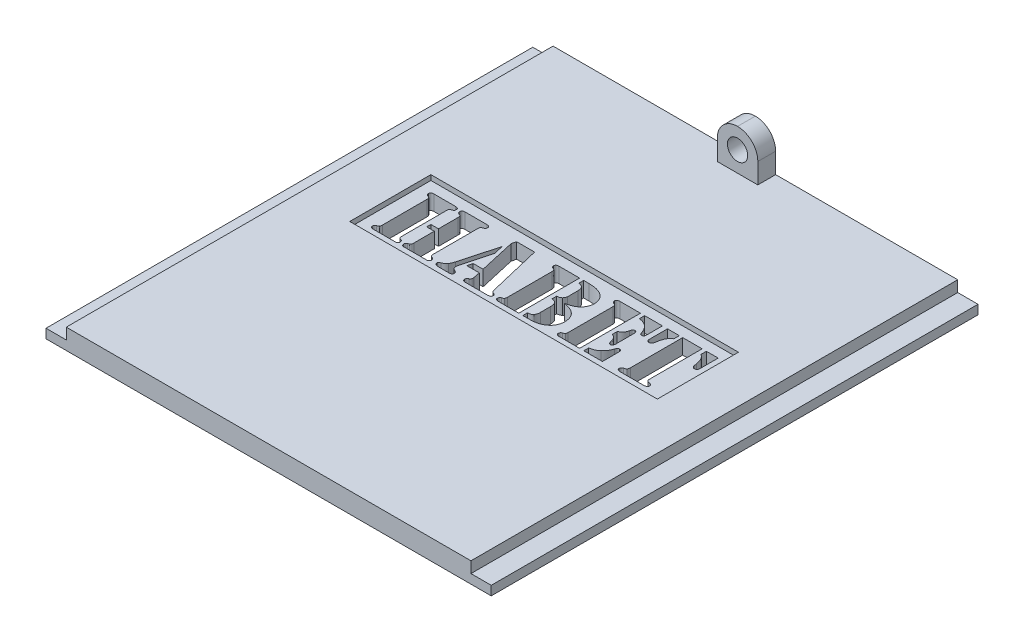
SolidWorks part; units mm, degrees
ref_plane "Front Plane" through (0, 0, 0) normal (0, 0, 1) x (1, 0, 0)
ref_plane "Top Plane" through (0, 0, 0) normal (0, 1, 0) x (1, 0, 0)
ref_plane "Right Plane" through (0, 0, 0) normal (1, 0, 0) x (0, 0, -1)
sketch "Sketch1" plane through (0, 0, 0) normal (0, 1, 0) x (1, 0, 0)
  line L1 (0, 0) -> (139.4003, 0)
  line L2 (0, 0) -> (0, 152.4)
  line L3 (0, 152.4) -> (139.4003, 152.4)
  line L4 (139.4003, 0) -> (139.4003, 152.4)
  dimension "D1" = 152.4
  dimension "D2" = 139.4003
extrude "Boss-Extrude1" add sketch "Sketch1" along normal blind 6.35
sketch "Sketch2" plane through (0, 6.35, 0) normal (0, 1, 0) x (1, 0, 0)
  line L0 (0, 0) -> (139.4003, 0) construction
  line L1 (0, 152.4) -> (6.35, 152.4)
  line L2 (0, 152.4) -> (0, 0)
  line L3 (0, 0) -> (6.35, 0)
  line L4 (6.35, 152.4) -> (6.35, 0)
  line L6 (139.4003, 152.4) -> (133.0503, 152.4)
  line L7 (139.4003, 152.4) -> (139.4003, 0)
  line L8 (139.4003, 0) -> (133.0503, 0)
  line L9 (133.0503, 152.4) -> (133.0503, 0)
  dimension "D1" = 6.35
  dimension "D2" = 6.35
extrude "Cut-Extrude1" cut sketch "Sketch2" against normal blind 3.4747
sketch "Sketch3" plane through (0, 6.35, 0) normal (0, 1, 0) x (1, 0, 0)
  line L0 (133.0503, 152.4) -> (6.35, 152.4) construction
  line L1 (63.3501, 152.4) -> (76.0501, 152.4)
  line L2 (63.3501, 152.4) -> (63.3501, 146.8137)
  line L3 (63.3501, 146.8137) -> (76.0501, 146.8137)
  line L4 (76.0501, 152.4) -> (76.0501, 146.8137)
  point P6 (69.7001, 152.4)
  point P7 (69.7001, 152.4)
  dimension "D1" = 12.7
extrude "Boss-Extrude2" add sketch "Sketch3" along normal blind 12.7
fillet "Fillet1" radius 6.35 2 edges at (63.3501, 19.05, -149.6068) (76.0501, 19.05, -149.6068)
sketch "Sketch4" plane through (0, 0, -152.4) normal (0, 0, -1) x (-1, 0, 0)
  circle A0 centre (-69.7001, 12.7) radius 3.175
  arc A1 (-63.3501, 12.7) -> (-69.7001, 19.05) centre (-69.7001, 12.7) ccw construction
  dimension "D1" = 3.175
extrude "Cut-Extrude2" cut sketch "Sketch4" against normal blind 6.35
sketch "Sketch7" plane through (0, 6.35, 0) normal (0, 1, 0) x (1, 0, 0)
  line L0 (6.35, 76.2) -> (133.0503, 76.2) construction
  line L3 (6.35, 0) -> (6.35, 152.4) construction
  line L4 (133.0503, 152.4) -> (133.0503, 0) construction
  text T0 "HABET" font "Stencil" height 19.05
extrude "Cut-Extrude7" cut sketch "Sketch7" against normal blind 6.35
sketch "Sketch9" plane through (0, 6.35, 0) normal (0, 1, 0) x (1, 0, 0)
  line L0 (35.9699, 95.25) -> (42.8243, 95.25) construction
  line L1 (22.0751, 98.425) -> (118.3835, 98.425)
  line L2 (22.0751, 98.425) -> (22.0751, 73.025)
  line L3 (22.0751, 73.025) -> (118.3835, 73.025)
  line L4 (118.3835, 98.425) -> (118.3835, 73.025)
  line L5 (42.8243, 76.2) -> (35.941, 76.2) construction
  line L6 (115.2085, 95.25) -> (115.2085, 89.5036) construction
  point P7 (39.3971, 95.25)
  point P10 (39.3826, 76.2)
  dimension "D1" = 3.175
  dimension "D2" = 3.175
  dimension "D3" = 3.175
  dimension "D4" = 3.175
extrude "Cut-Extrude8" cut sketch "Sketch9" against normal blind 1.5875
